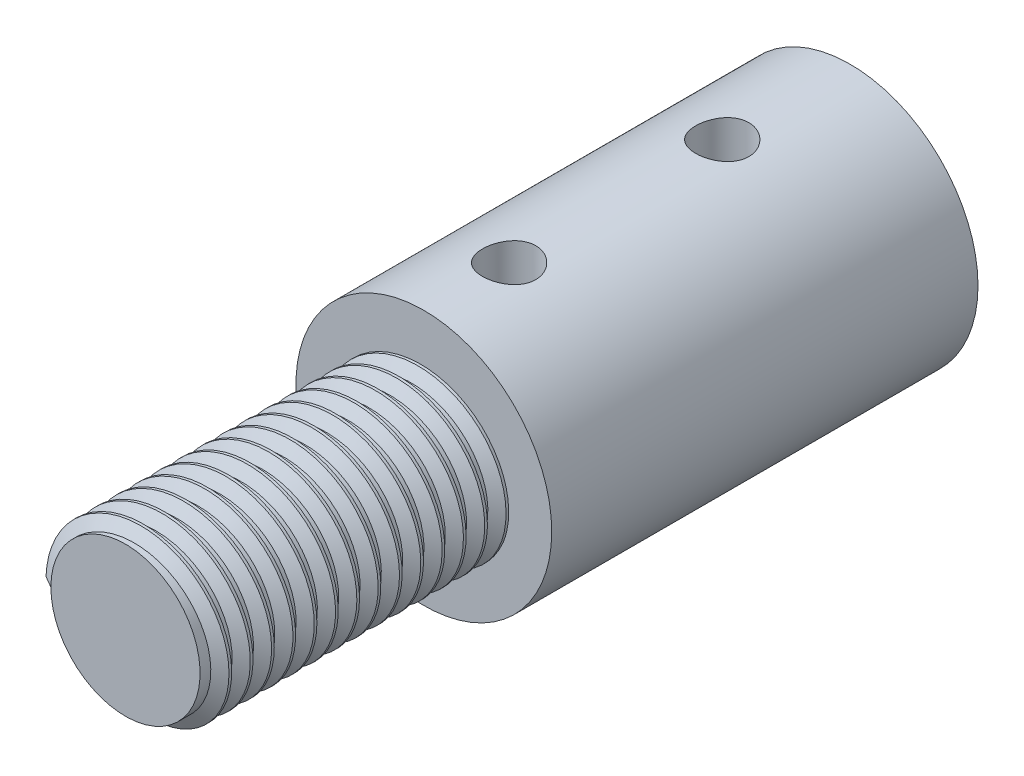
SolidWorks part; units mm, degrees
ref_plane "前视基准面" through (0, 0, 0) normal (0, 0, 1) x (1, 0, 0)
ref_plane "上视基准面" through (0, 0, 0) normal (0, 1, 0) x (1, 0, 0)
ref_plane "右视基准面" through (0, 0, 0) normal (1, 0, 0) x (0, 0, -1)
sketch "草图1" plane through (0, 0, 0) normal (0, 0, 1) x (1, 0, 0)
  circle A0 centre (0, 0) radius 6
  circle A1 centre (0, 0) radius 2.1
  dimension "D1" = 12
  dimension "D2" = 4.2
extrude "凸台-拉伸1" add sketch "草图1" along normal blind 34 contours A0
extrude "切除-拉伸2" cut sketch "草图1<3>" along normal blind 11 contours A1 region at (0, 0, 0)
sketch "草图1<3>" plane through (0, 0, 0) normal (0, 0, 1) x (1, 0, 0) same geometry as "草图1"
ref_axis "基准轴1" through (0, 0, 23.7715) along (0, 0, -1)
sketch "草图2" plane through (0, 0, 0) normal (0, 1, 0) x (1, 0, 0)
  line L1 (0, -23.7715) -> (0, 6.6627) construction
  circle A0 centre (0, -6) radius 1.25
  dimension "D1" = 2.5
  dimension "D2" = 6
extrude "切除-拉伸3" cut sketch "草图2" along normal through all
sketch "草图3" plane through (0, 0, 0) normal (1, 0, 0) x (0, 0, -1)
  line L0 (-23.7715, 0) -> (6.6627, 0) construction
  circle A0 centre (-6, 0) radius 1.25
  dimension "D1" = 2.5
  dimension "D2" = 6
sketch "草图4" plane through (0, 0, 0) normal (0, 1, 0) x (1, 0, 0)
  line L1 (0, -23.7715) -> (0, 6.6627) construction
  line L2 (6, 0) -> (-6, 0) construction
  circle A0 centre (0, -16) radius 1.25
  dimension "D1" = 2.5
  dimension "D2" = 16
extrude "切除-拉伸5" cut sketch "草图4" along normal through all
sketch "草图5" plane through (0, 0, 0) normal (1, 0, 0) x (0, 0, -1)
  line L0 (-23.7715, 0) -> (6.6627, 0) construction
  line L2 (0, -6) -> (0, 6) construction
  circle A0 centre (-16, 0) radius 3.1
  dimension "D1" = 6.2
  dimension "D2" = 16
extrude "切除-拉伸6" cut sketch "草图5" against normal through all and the other way blind 2
sketch "草图8" plane through (0, 0, 34) normal (0, 0, 1) x (1, 0, 0)
  circle A0 centre (0, 0) radius 3.5
  circle A1 centre (0, 0) radius 6 construction
  circle A2 centre (0, 0) radius 6
  dimension "D1" = 7
extrude "切除-拉伸7" cut sketch "草图8" against normal blind 14
thread "螺纹线1" pitch 1 method extrude profile "螺纹线轮廓3" start angle 0, offset 0, length 0, pitch 1, diameter 7
ref_plane "基准面3" through (-3.5, 0, 34) normal (0, -1, 0) x (-1, 0, 0)
sketch "螺纹线轮廓3" plane through (-3.5, 0, 34) normal (0, -1, 0) x (-1, 0, 0)
  line L0 (0, 0) -> (0, 1) construction
  line L1 (0, 0) -> (0.5413, 0.3125)
  line L2 (0.5413, 0.3125) -> (0.5413, 0.4375)
  line L3 (0.5413, 0.4375) -> (0, 0.75)
  line L4 (0.5413, 0.375) -> (0, 0.375) construction
  line L11 (0, 0) -> (0, 0.75)
  point P2 (0, 0)
  dimension "Pitch" = 1
  dimension "Profile_Angle" = 60
  dimension "Profile_Land" = 0.125
  dimension "Profile_Height" = 0.5413
